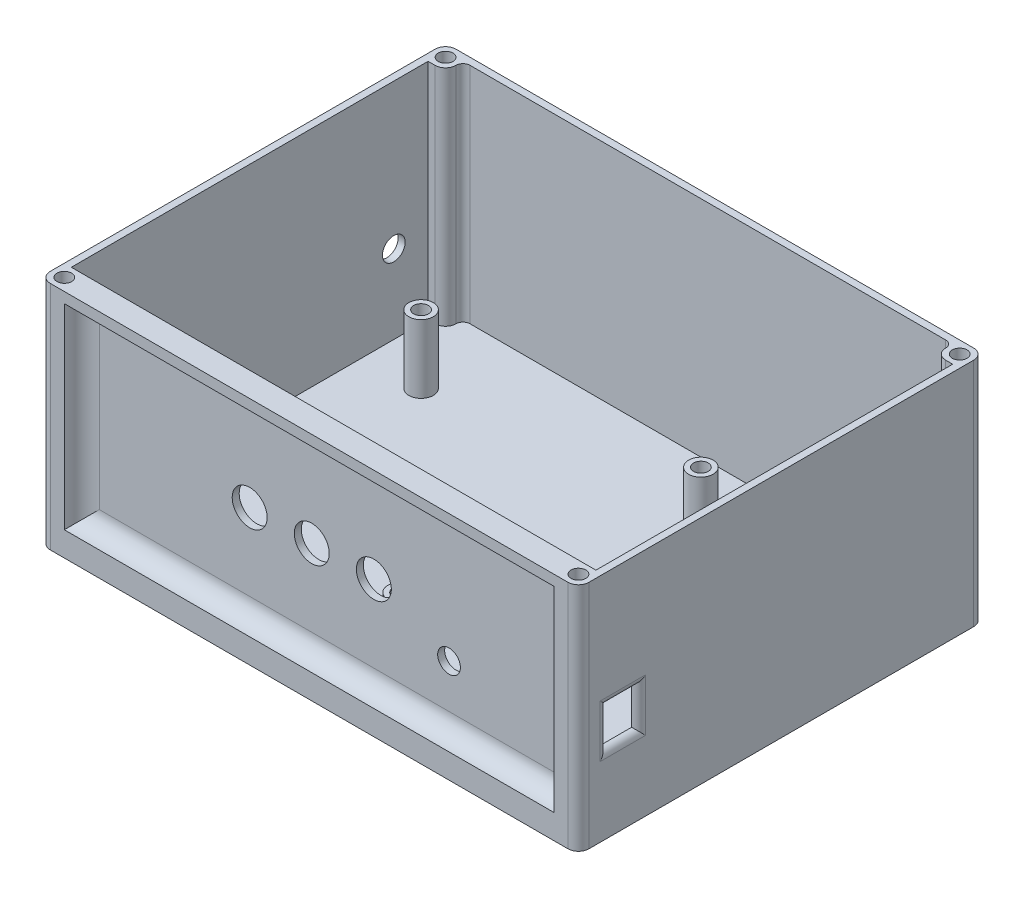
SolidWorks part; units mm, degrees
ref_plane "Front Plane" through (0, 0, 0) normal (0, 0, 1) x (1, 0, 0)
ref_plane "Top Plane" through (0, 0, 0) normal (0, 1, 0) x (1, 0, 0)
ref_plane "Right Plane" through (0, 0, 0) normal (1, 0, 0) x (0, 0, -1)
sketch "Sketch1" plane through (0, 0, 0) normal (0, 1, 0) x (1, 0, 0)
  line L1 (-77, 58) -> (77, 58)
  line L2 (-77, 58) -> (-77, -58)
  line L3 (-77, -58) -> (77, -58)
  line L4 (77, 58) -> (77, -58)
  line L5 (-77, 58) -> (77, -58) construction
  line L6 (-77, -58) -> (77, 58) construction
  point P0 (0, 0)
  dimension "D1" = 154
  dimension "D2" = 116
extrude "Boss-Extrude1" add sketch "Sketch1" along normal blind 70
sketch "Sketch2" plane through (0, 70, 0) normal (0, 1, 0) x (1, 0, 0)
  line L1 (-75, 51) -> (75, 51)
  line L2 (-75, 51) -> (-75, -51)
  line L3 (-75, -51) -> (75, -51)
  line L4 (75, 51) -> (75, -51)
  line L5 (-75, 51) -> (75, -51) construction
  line L6 (-75, -51) -> (75, 51) construction
  point P0 (0, 0)
  dimension "D1" = 150
  dimension "D2" = 102
extrude "Cut-Extrude1" cut sketch "Sketch2" against normal blind 68
sketch "Sketch3" plane through (0, 70, 0) normal (0, 1, 0) x (1, 0, 0)
  line L0 (75, 51) -> (-75, 51) construction
  line L1 (77, -58) -> (77, 58) construction
  line L3 (70, 51) -> (-70, 51)
  line L4 (70, 51) -> (70, 56)
  line L5 (70, 56) -> (-70, 56)
  line L6 (-70, 51) -> (-70, 56)
  point P0 (70, 51)
  dimension "D1" = 7
  dimension "D2" = 5
  dimension "D3" = 140
extrude "Cut-Extrude2" cut sketch "Sketch3" against normal blind 68
sketch "Sketch5" plane through (0, 0, 58) normal (0, 0, 1) x (1, 0, 0)
  line L0 (0, 0) -> (0, 70)
  line L1 (-77, 0) -> (77, 0) construction
  line L2 (-77, 70) -> (77, 70) construction
  line L4 (-70, 7) -> (70, 7)
  line L5 (-70, 7) -> (-70, 63)
  line L6 (-70, 63) -> (70, 63)
  line L7 (70, 7) -> (70, 63)
  line L8 (-70, 7) -> (70, 63) construction
  line L9 (-70, 63) -> (70, 7) construction
  point P6 (0, 35)
  dimension "D1" = 56
  dimension "D2" = 140
extrude "Cut-Extrude4" cut sketch "Sketch5" against normal blind 5 contours L4 L7 L6 L0 | L6 L5 L4 L0 region at (-35, 35, 58) region at (35, 35, 58)
sketch "Sketch6" plane through (0, 70, 0) normal (0, 1, 0) x (1, 0, 0)
  line L0 (77, 58) -> (-77, 58) construction
  line L1 (77, -58) -> (77, 58) construction
  line L5 (-77, 58) -> (-77, -58) construction
  line L6 (-77, -58) -> (77, -58) construction
  circle A0 centre (73.5, 54.5) radius 1.5
  circle A1 centre (-73.5, 54.5) radius 1.5
  circle A2 centre (73.5, -54.5) radius 1.5
  circle A3 centre (-73.5, -54.5) radius 1.5
  point P0 (73.5, 54.5)
  point P7 (-73.5, 54.5)
  point P8 (73.5, -54.5)
  point P17 (-73.5, -54.5)
  point P18 (-93.3302, -64.696)
  dimension "D3" = 3
  dimension "D6" = 3
  dimension "D8" = 3
  dimension "D9" = 3
  dimension "D1" = 3.5
  dimension "D2" = 3.5
  dimension "D4" = 3.5
  dimension "D5" = 3.5
  dimension "D7" = 3.5
sketch "Sketch17" plane through (75, 0, 0) normal (-1, 0, 0) x (0, 0, 1)
  line L0 (51, 2) -> (51, 70) construction
  line L1 (51, 2) -> (-51, 2) construction
  line L3 (49.8, 22) -> (40.8, 22)
  line L4 (49.8, 22) -> (49.8, 33)
  line L5 (49.8, 33) -> (40.8, 33)
  line L6 (40.8, 22) -> (40.8, 33)
  point P0 (49.8, 22)
  dimension "D1" = 1.2
  dimension "D2" = 20
  dimension "D3" = 9
  dimension "D4" = 11
extrude "Cut-Extrude12" cut sketch "Sketch17" against normal through all
fillet "Fillet1" radius 2 4 edges at (77, 22, 45.3) (77, 27.5, 49.8) (77, 33, 45.3) (77, 27.5, 40.8) type face fillet first side face at (76, 27.5, 40.8) first side face at (76, 33, 45.3) first side face at (76, 27.5, 49.8) first side face at (76, 22, 45.3) second side face at (77, 27.5, 45.3)
fillet "Fillet3" radius 5 4 edges at (0, 7, 53) (-70, 35, 53) (0, 63, 53) (70, 35, 53) type face fillet first side face at (0, 7, 55.5) first side face at (70, 35, 55.5) first side face at (0, 63, 55.5) first side face at (-70, 35, 55.5) second side face at (0, 70, -26.75) second side face at (0, 35, 53)
fillet "Fillet4" radius 3 1 edges at (77, 35, 58) type face fillet first side face at (0, 35, 58) second side face at (77, 27.5, 45.3)
fillet "Fillet5" radius 3 1 edges at (-77, 35, 58) type face fillet first side face at (-77, 35, 0) second side face at (0, 35, 58)
fillet "Fillet6" radius 3 1 edges at (-77, 35, -58) type face fillet first side face at (0, 35, -58) second side face at (-77, 35, -1.5)
fillet "Fillet7" radius 3 1 edges at (77, 35, -58) type face fillet first side face at (77, 27.5, 45.3) second side face at (1.5, 35, -58)
fillet "Fillet9" radius 3 1 edges at (-70, 36, -51) type face fillet first side face at (-70, 36, -53.5) second side face at (-72.5, 36, -51)
fillet "Fillet11" radius 2 1 edges at (-70, 36, -56) type face fillet first side face at (0, 36, -56) second side face at (-70, 36, -55)
fillet "Fillet12" radius 3 1 edges at (70, 36, -51) type face fillet first side face at (72.5, 36, -51) second side face at (70, 36, -53.5)
fillet "Fillet13" radius 2 1 edges at (70, 36, -56) type face fillet first side face at (70, 36, -55) second side face at (1, 36, -56)
sketch "Sketch18" plane through (0, 70, 0) normal (0, 1, 0) x (1, 0, 0)
  line L1 (77, 58) -> (-77, 58)
  line L2 (77, 58) -> (77, -58)
  line L3 (77, -58) -> (-77, -58)
  line L4 (-77, 58) -> (-77, -58)
  line L5 (77, 58) -> (-77, -58) construction
  line L6 (77, -58) -> (-77, 58) construction
  point P0 (0, 0)
  dimension "D1" = 116
  dimension "D2" = 154
extrude "Cut-Extrude13" cut sketch "Sketch18" against normal blind 4
sketch "Sketch19" plane through (0, 0, 51) normal (0, 0, -1) x (-1, 0, 0)
  line L0 (75, 2) -> (-75, 2) construction
  line L1 (75, 2) -> (75, 66) construction
  circle A0 centre (-13.5, 34) radius 5
  circle A1 centre (4.25, 34) radius 5
  circle A2 centre (22, 34) radius 5
  point P0 (22, 34)
  point P3 (4.25, 34)
  point P4 (-13.5, 34)
  dimension "D5" = 10
  dimension "D6" = 10
  dimension "D7" = 10
  dimension "D1" = 32
  dimension "D2" = 53
  dimension "D3" = 70.75
  dimension "D4" = 88.5
extrude "Cut-Extrude14" cut sketch "Sketch19" against normal blind 4
sketch "Sketch20" plane through (0, 2, 0) normal (0, 1, 0) x (1, 0, 0)
  line L0 (-75, 51) -> (-75, -51) construction
  line L1 (-75, -51) -> (75, -51) construction
  circle A0 centre (-60, -36) radius 3.5
  circle A1 centre (8, -40) radius 3.5
  circle A2 centre (-59, 33) radius 3.5
  circle A3 centre (20, 34) radius 3.5
  point P0 (-60, -36)
  point P7 (-59, 33)
  point P8 (8, -40)
  point P9 (20, 34)
  dimension "D3" = 7
  dimension "D6" = 7
  dimension "D9" = 7
  dimension "D12" = 7
  dimension "D1" = 15
  dimension "D2" = 15
  dimension "D4" = 83
  dimension "D5" = 11
  dimension "D7" = 16
  dimension "D8" = 84
  dimension "D10" = 95
  dimension "D11" = 85
extrude "Boss-Extrude3" add sketch "Sketch20" along normal blind 19.5
sketch "Sketch21" plane through (0, 21.5, 0) normal (0, 1, 0) x (1, 0, 0)
  circle A0 centre (-59, 33) radius 1.5
  circle A1 centre (20, 34) radius 1.5
  circle A2 centre (8, -40) radius 1.5
  circle A3 centre (-60, -36) radius 1.5
  dimension "D1" = 3
  dimension "D2" = 3
  dimension "D3" = 3
  dimension "D4" = 3
sketch "Sketch22" plane through (0, 2, 0) normal (0, 1, 0) x (1, 0, 0)
  line L0 (75, -51) -> (75, 51) construction
  line L1 (-75, -51) -> (75, -51) construction
  circle A0 centre (50, 29) radius 3.5
  circle A1 centre (35, 3) radius 3.5
  circle A2 centre (67, 3) radius 3.5
  circle A3 centre (54, -44) radius 3.5
  point P0 (54, -44)
  point P1 (35, 3)
  point P2 (67, 3)
  point P3 (50, 29)
  dimension "D9" = 7
  dimension "D10" = 7
  dimension "D11" = 7
  dimension "D12" = 7
  dimension "D1" = 21
  dimension "D2" = 7
  dimension "D3" = 54
  dimension "D4" = 54
  dimension "D5" = 80
  dimension "D6" = 25
  dimension "D7" = 8
  dimension "D8" = 40
extrude "Boss-Extrude4" add sketch "Sketch22" along normal blind 18
sketch "Sketch23" plane through (0, 20, 0) normal (0, 1, 0) x (1, 0, 0)
  circle A0 centre (35, 3) radius 1.5
  circle A1 centre (50, 29) radius 1.5
  circle A2 centre (67, 3) radius 1.5
  circle A3 centre (54, -44) radius 1.5
  dimension "D1" = 3
  dimension "D2" = 3
  dimension "D3" = 3
  dimension "D4" = 3
sketch "Sketch24" plane through (0, 0, 51) normal (0, 0, -1) x (-1, 0, 0)
  line L0 (75, 2) -> (-75, 2) construction
  line L1 (-75, 2) -> (-75, 66) construction
  circle A0 centre (-35, 24.5) radius 3.25
  point P0 (-35, 24.5)
  dimension "D3" = 6.5
  dimension "D1" = 22.5
  dimension "D2" = 40
extrude "Cut-Extrude17" cut sketch "Sketch24" against normal through all
sketch "Sketch25" plane through (-75, 0, 0) normal (1, 0, 0) x (0, 0, -1)
  line L0 (51, 2) -> (-51, 2) construction
  line L1 (-51, 2) -> (-51, 66) construction
  circle A0 centre (-44, 24.5) radius 3.25
  circle A1 centre (41.2, 24.5) radius 3.25
  point P0 (-44, 24.5)
  point P1 (41.2, 24.5)
  dimension "D5" = 6.5
  dimension "D6" = 6.5
  dimension "D1" = 22.5
  dimension "D2" = 22.5
  dimension "D3" = 7
  dimension "D4" = 92.2
extrude "Cut-Extrude18" cut sketch "Sketch25" against normal through all
extrude "Cut-Extrude19" cut sketch "Sketch6" against normal blind 60
sketch "Sketch26" plane through (0, 66, 0) normal (0, 1, 0) x (1, 0, 0)
  circle A0 centre (73.5, -54.5) radius 2.1
  circle A1 centre (73.5, 54.5) radius 2.1
  circle A2 centre (-73.5, 54.5) radius 2.1
  circle A3 centre (-73.5, -54.5) radius 2.1
  dimension "D1" = 4.2
  dimension "D2" = 4.2
  dimension "D3" = 4.2
  dimension "D4" = 4.2
extrude "Cut-Extrude20" cut sketch "Sketch26" against normal blind 10
extrude "Cut-Extrude21" cut sketch "Sketch23" against normal blind 15
sketch "Sketch27" plane through (0, 20, 0) normal (0, 1, 0) x (1, 0, 0)
  circle A0 centre (54, -44) radius 2.1
  circle A1 centre (35, 3) radius 2.1
  circle A2 centre (50, 29) radius 2.1
  circle A3 centre (67, 3) radius 2.1
  dimension "D1" = 4.2
  dimension "D2" = 4.2
  dimension "D3" = 4.2
  dimension "D4" = 4.2
extrude "Cut-Extrude22" cut sketch "Sketch27" against normal blind 10
extrude "Cut-Extrude23" cut sketch "Sketch21" against normal blind 15
sketch "Sketch28" plane through (0, 21.5, 0) normal (0, 1, 0) x (1, 0, 0)
  circle A0 centre (-59, 33) radius 2.1
  circle A1 centre (-60, -36) radius 2.1
  circle A2 centre (8, -40) radius 2.1
  circle A3 centre (20, 34) radius 2.1
  dimension "D1" = 4.2
  dimension "D2" = 4.2
  dimension "D3" = 4.2
  dimension "D4" = 4.2
extrude "Cut-Extrude24" cut sketch "Sketch28" against normal blind 10
